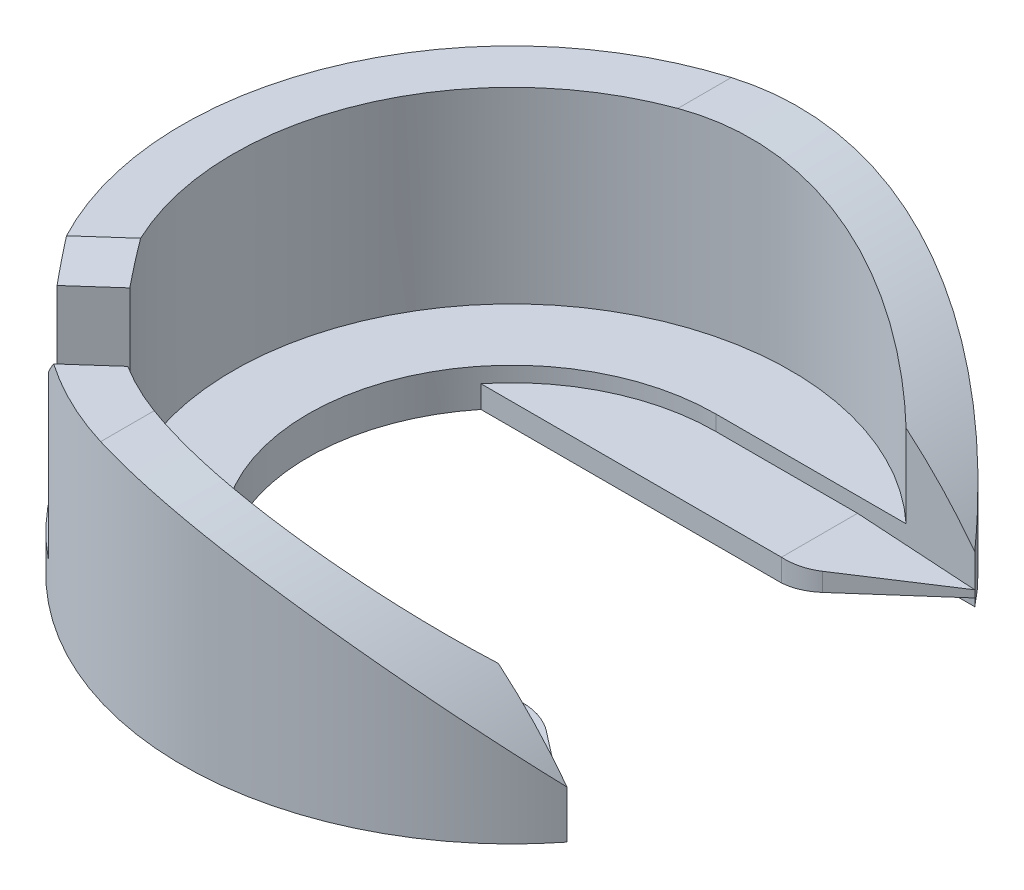
SolidWorks part; units mm, degrees
ref_plane "Front Plane" through (0, 0, 0) normal (0, 0, 1) x (1, 0, 0)
ref_plane "Top Plane" through (0, 0, 0) normal (0, 1, 0) x (1, 0, 0)
ref_plane "Right Plane" through (0, 0, 0) normal (1, 0, 0) x (0, 0, -1)
sketch "Sketch1" plane through (0, 0, 0) normal (0, 1, 0) x (1, 0, 0)
  line L0 (-31.3209, 25.2) -> (31.3209, 25.2)
  line L1 (-31.3209, -25.2) -> (31.3209, -25.2)
  line L2 (0, 40.2) -> (51.078, 40.2)
  line L3 (31.3209, 25.2) -> (59.9163, 25.2)
  line L4 (-65, 0) -> (65, 0) construction
  line L5 (31.3209, -25.2) -> (59.9163, -25.2)
  line L6 (0, -40.2) -> (51.078, -40.2)
  line L7 (31.3209, -25.2) -> (51.078, -40.2)
  line L8 (31.3209, 25.2) -> (51.078, 40.2)
  circle A0 centre (0, 0) radius 40.2
  circle A1 centre (0, 0) radius 55
  circle A2 centre (0, 0) radius 65
  point P14 (0, 0)
  dimension "D1" = 80.4
  dimension "D3" = 110
  dimension "D4" = 130
  dimension "D2" = 25.2
extrude "Boss-Extrude1" add sketch "Sketch1" along normal blind 4.4 contours A0 L1 | L6 A1 L5 A0 | L4 A2 L6 A1 | L4 A1 L6 A0 | A1 L4 A0 L2 | A2 L4 A1 L2 | L0 A0 | L3 A1 L2 A0 | A1 L8 L2 | A1 L6 L7 region at (0, 0, -31.3077) region at (-38.9306, 0, -13.717) region at (28.9153, 0, -35.1135) region at (-38.9306, 0, 13.717) region at (43.9832, 0, -38.2044) region at (-22.4449, 0, -51.6657) region at (-22.4449, 0, 51.6657) region at (0, 0, 31.3077) region at (28.9153, 0, 35.1135) region at (43.9832, 0, 38.2044)
extrude "Boss-Extrude2" add sketch "Sketch1<3>" along normal blind 40 from surface contours L4 A2 L6 A1 | A2 L4 A1 L2 region at (-22.4449, 0, -51.6657) region at (-22.4449, 0, 51.6657) starting at face at (-3.8002, 4.4, 0)
sketch "Sketch1<3>" plane through (0, 0, 0) normal (0, 1, 0) x (1, 0, 0) same geometry as "Sketch1"
extrude "Boss-Extrude3" add sketch "Sketch1<4>" along normal blind 3 from surface contours A1 L4 A0 L2 | L4 A1 L6 A0 region at (-38.9306, 0, -13.717) region at (-38.9306, 0, 13.717) starting at face at (9.4766, 4.4, 0)
sketch "Sketch1<4>" plane through (0, 0, 0) normal (0, 1, 0) x (1, 0, 0) same geometry as "Sketch1"
sketch "Sketch2" plane through (0, 44.4, 0) normal (0, 1, 0) x (1, 0, 0)
  line L0 (0, 0) -> (-65, 0) construction
  line L1 (0, 0) -> (-48.5466, -43.223) construction
  line L2 (-54.8912, -34.8132) -> (-47.3045, -28.0585)
  line L3 (-40.9268, -50.4975) -> (-33.3402, -43.7428)
  circle A0 centre (0, 0) radius 65
  circle A1 centre (0, 0) radius 55
  arc M7 (37.5361, -40.2) -> (37.5361, 40.2) centre (0, 0) cw
  arc M9 (51.078, 40.2) -> (51.078, -40.2) centre (0, 0) ccw
  dimension "D1" = 130
  dimension "D2" = 110
  dimension "D3" = 41.68
  dimension "D4" = 21
extrude "Cut-Extrude1" cut sketch "Sketch2" against normal up to surface (37 mm away) contours L3 L2 M9 M7 region at (-44.5798, 44.4, 39.6913) up to face at (-14.416, 7.4, 0)
chamfer "Chamfer1" distance 5 angle 45 2 edges at (-37.1335, 44.4, 47.1201) (-51.0978, 44.4, 31.4359)
sketch "Sketch3" plane through (0, 0, -25.2) normal (0, 0, 1) x (1, 0, 0)
  line L0 (51.078, 44.4) -> (-18.922, 44.4)
  line L1 (51.078, 44.4) -> (-36.8391, 44.4) construction
  line L2 (51.078, 44.4) -> (51.078, 9.4)
  line L3 (51.078, 44.4) -> (51.078, 4.4) construction
  arc A0 (-18.922, 44.4) -> (51.078, 9.4) centre (-18.922, -43.1) cw
  dimension "D1" = 35
  dimension "D2" = 70
extrude "Cut-Extrude2" cut sketch "Sketch3" against normal through all both and the other way through all
fillet "Fillet1" radius 10 2 edges at (31.3209, 2.2, 25.2) (31.3209, 2.2, -25.2)
sketch "Sketch4" plane through (0, 0, -25.2) normal (0, 0, 1) x (1, 0, 0)
  line L0 (27.9549, 4.4) -> (51.078, 2.9)
  line L1 (51.078, 4.4) -> (51.078, 0) construction
  line L2 (51.078, 2.9) -> (51.078, 1.5)
  line L3 (51.078, 1.5) -> (27.9549, 0)
  line L4 (27.9549, 0) -> (51.078, 0)
  line L5 (51.078, 0) -> (51.078, 4.4)
  line L6 (51.078, 4.4) -> (27.9549, 4.4)
  dimension "D1" = 1.5
  dimension "D2" = 1.5
extrude "Cut-Extrude3" cut sketch "Sketch4" against normal up to surface (15 mm away) and the other way up to surface (65.4 mm away) contours L5 L6 L0 | L4 L5 L3 region at (43.3703, 3.9, -25.2) region at (43.3703, 0.5, -25.2) up to face at (29.6057, 9.5219, -40.2) other way up to face at (29.6057, 9.5219, 40.2)
